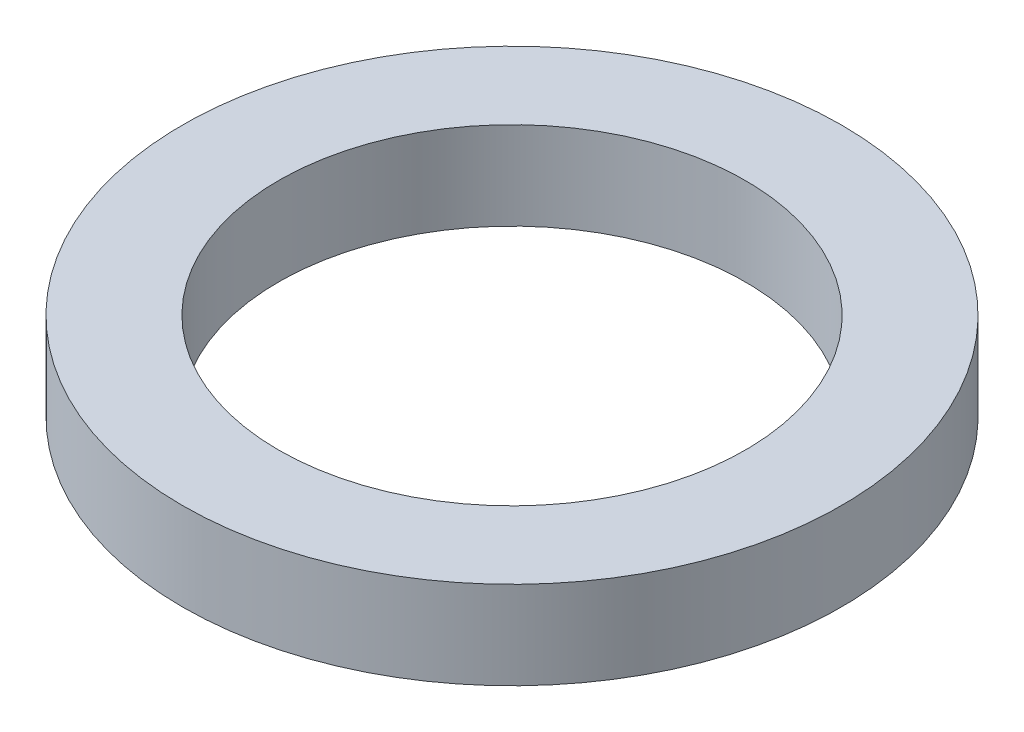
SolidWorks part; units mm, degrees
ref_plane "Front Plane" through (0, 0, 0) normal (0, 0, 1) x (1, 0, 0)
ref_plane "Top Plane" through (0, 0, 0) normal (0, 1, 0) x (1, 0, 0)
ref_plane "Right Plane" through (0, 0, 0) normal (1, 0, 0) x (0, 0, -1)
sketch "Sketch1" plane through (0, 0, 0) normal (0, 1, 0) x (1, 0, 0)
  circle A0 centre (0, 0) radius 60
  dimension "FLANGE_OD" = 120
extrude "Boss-Extrude1" add sketch "Sketch1" along normal blind 16
sketch "Sketch2" plane through (0, 0, 0) normal (0, 1, 0) x (1, 0, 0)
  circle A0 centre (0, 0) radius 42.5
  dimension "BORE_D" = 85
extrude "Cut-Extrude1" cut sketch "Sketch2" along normal through all
sketch "Sketch3" plane through (0, 16, 0) normal (0, 1, 0) x (1, 0, 0)
  circle A0 centre (0, 0) radius 25.9981 construction
  circle A1 centre (-25.9981, 0) radius 1.6097
  dimension "BOLT_D" = 3.2194
  dimension "BOLT_PCD" = 51.9961
extrude "Cut-Extrude2" cut sketch "Sketch3" against normal blind 14.4028 rebuild error yes
pattern_circular "CirPattern1" count 4 over 360 rebuild error yes
